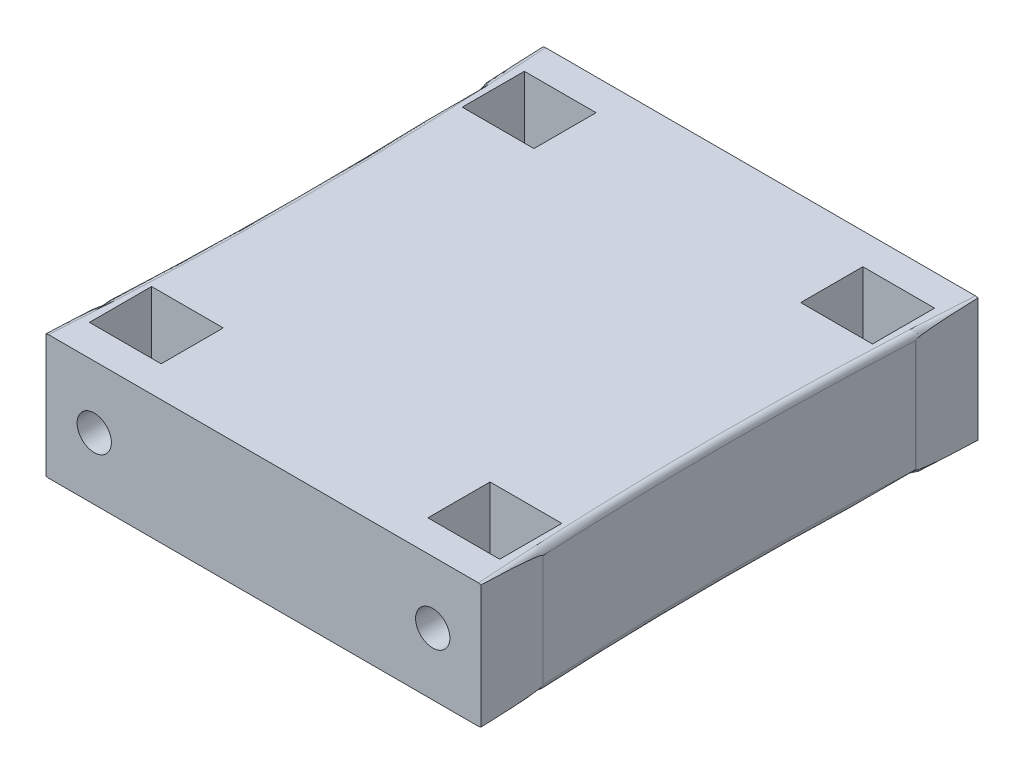
SolidWorks part; units mm, degrees
ref_plane "Front Plane" through (0, 0, 0) normal (0, 0, 1) x (1, 0, 0)
ref_plane "Top Plane" through (0, 0, 0) normal (0, 1, 0) x (1, 0, 0)
ref_plane "Right Plane" through (0, 0, 0) normal (1, 0, 0) x (0, 0, -1)
sketch "Sketch1" plane through (0, 0, 0) normal (0, 0, 1) x (1, 0, 0)
  line L0 (0, 0) -> (44.45, 0)
  line L1 (44.45, 0) -> (44.45, 12.7)
  line L2 (44.45, 12.7) -> (0, 12.7)
  line L3 (0, 12.7) -> (0, 0)
  line L4 (0, 6.35) -> (44.45, 6.35) construction
  circle A0 centre (4.9276, 6.35) radius 1.7526
  circle A1 centre (39.5224, 6.35) radius 1.7526
  point P11 (41.275, 6.35)
  point P13 (3.175, 6.35)
  dimension "D5" = 3.5052
  dimension "D1" = 12.7
  dimension "D2" = 44.45
  dimension "D3" = 3.175
  dimension "D4" = 3.175
extrude "Boss-Extrude1" add sketch "Sketch1" along normal mid plane 50.8
sketch "Sketch2" plane through (0, 0, 25.4) normal (0, 0, 1) x (1, 0, 0)
  line L0 (1.2614, 6.35) -> (1.2614, 14.9158)
  line L3 (1.2614, 6.35) -> (3.0945, 3.175)
  line L4 (3.0945, 3.175) -> (6.7607, 3.175)
  line L5 (6.7607, 3.175) -> (8.5938, 6.35)
  line L9 (35.8562, 6.35) -> (37.6893, 3.175)
  line L10 (37.6893, 3.175) -> (41.3555, 3.175)
  line L11 (41.3555, 3.175) -> (43.1886, 6.35)
  line L13 (1.2614, 14.9158) -> (8.5938, 14.9158)
  line L14 (8.5938, 14.9158) -> (8.5938, 6.35)
  line L15 (35.8562, 6.35) -> (35.8562, 16.0665)
  line L16 (35.8562, 16.0665) -> (43.1886, 16.0665)
  line L17 (43.1886, 16.0665) -> (43.1886, 6.35)
  line L19 (8.5938, 6.35) -> (7.6772, 7.9375) [skipped]
  line L20 (3.0945, 9.525) -> (2.178, 7.9375) [skipped]
  line L21 (4.9276, 9.525) -> (3.0945, 9.525) [skipped]
  line L22 (37.6893, 9.525) -> (36.7728, 7.9375) [skipped]
  line L23 (41.3555, 9.525) -> (37.6893, 9.525) [skipped]
  line L24 (43.1886, 6.35) -> (42.272, 7.9375) [skipped]
  line L25 (0, 0) -> (44.45, 0) construction
  arc A1 (36.7728, 4.7625) -> (42.272, 4.7625) centre (39.5224, 6.35) ccw construction
  arc A2 (2.178, 4.7625) -> (7.6772, 4.7625) centre (4.9276, 6.35) ccw construction
  dimension "D1" = 3.175
  dimension "D2" = 14.9158
  dimension "D3" = 16.0665
extrude "Cut-Extrude1" cut sketch "Sketch2" against normal blind 6.35 from offset 3.175 offset against normal yes
extrude "Cut-Extrude2" cut sketch "Sketch2<2>" along normal blind 6.35 from offset 47.625 offset against normal yes
sketch "Sketch2<2>" plane through (0, 0, 25.4) normal (0, 0, 1) x (1, 0, 0) same geometry as "Sketch2"
sketch "Sketch3" plane through (0, 0, 0) normal (0, -1, 0) x (1, 0, 0)
  line L0 (44.45, 25.4) -> (44.45, -25.4) construction
  line L1 (44.45, 25.4) -> (44.45, -25.4) construction
  line L2 (44.45, 19.05) -> (44.45, -19.05)
  line L3 (22.225, 25.4) -> (22.225, -25.4) construction
  line L4 (0, 25.4) -> (44.45, 25.4) construction
  line L5 (0, -25.4) -> (44.45, -25.4) construction
  line L6 (0, 19.05) -> (0, -19.05)
  arc A0 (44.45, 19.05) -> (44.45, -19.05) centre (418.5137, 0) ccw
  arc A1 (0, 19.05) -> (0, -19.05) centre (-374.0637, 0) cw
  dimension "D1" = 6.35
  dimension "D2" = 6.35
extrude "Cut-Extrude3" cut sketch "Sketch3" against normal through all
fillet "Fillet1" radius 0.635 8 edges at (44.45, 6.35, 19.05) (43.9652, 12.7, 0) (44.45, 6.35, -19.05) (43.9652, 0, 0) (0, 6.35, -19.05) (0.4848, 12.7, 0) (0, 6.35, 19.05) (0.4848, 0, 0)
